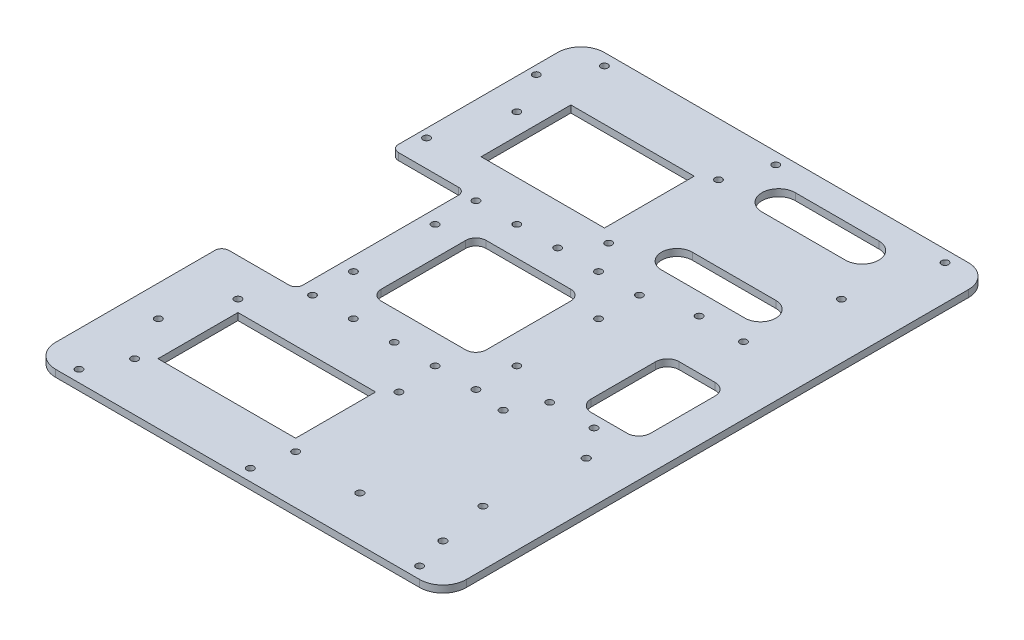
SolidWorks part; units mm, degrees
ref_plane "前视基准面" through (0, 0, 0) normal (0, 0, 1) x (1, 0, 0)
ref_plane "上视基准面" through (0, 0, 0) normal (0, 1, 0) x (1, 0, 0)
ref_plane "右视基准面" through (0, 0, 0) normal (1, 0, 0) x (0, 0, -1)
other "Configuration Table"
sketch "草图2" plane through (0, 0, 0) normal (0, 1, 0) x (1, 0, 0)
  line L0 (0, 0) -> (34826.5103, 0) construction
  line L1 (0, 0) -> (0, -34826.5103) construction
  line L2 (-72.5, -36.2939) -> (-72.5, -107.5)
  line L4 (-72.5, 107.5) -> (-72.5, 36.2939)
  line L7 (-62.5, 117.5) -> (93.3866, 117.5)
  line L8 (-62.5, -117.5) -> (93.3866, -117.5)
  line L15 (-35, 35) -> (35, 35) construction
  line L16 (-35, 35) -> (-35, -35) construction
  line L17 (-35, -35) -> (35, -35) construction
  line L18 (35, 35) -> (35, -35) construction
  line L19 (-35, 35) -> (35, -35) construction
  line L20 (-35, -35) -> (35, 35) construction
  line L21 (-18.1, 22.5) -> (18.1, 22.5)
  line L22 (-22.5, 18.1) -> (-22.5, -18.1)
  line L23 (-18.1, -22.5) -> (18.1, -22.5)
  line L24 (22.5, 18.1) -> (22.5, -18.1)
  line L25 (-22.5, 22.5) -> (22.5, -22.5) construction
  line L26 (-22.5, -22.5) -> (22.5, 22.5) construction
  line L30 (103.3866, 107.5) -> (103.3866, -107.5)
  line L32 (-49.5097, -52.4041) -> (-49.5097, -96.6641) construction
  line L33 (-72.5, -36.2939) -> (-40.7785, -36.2939)
  line L35 (-72.5, 36.2939) -> (-40.7785, 36.2939)
  line L36 (-40.7785, -36.2939) -> (-40.7785, 36.2939)
  line L37 (-49.5097, -96.6641) -> (19.4403, -96.6641) construction
  line L38 (19.4403, -52.4041) -> (19.4403, -96.6641) construction
  line L39 (-49.5097, -52.4041) -> (19.4403, -52.4041) construction
  line L40 (-44.5097, -57.4041) -> (-44.5097, -91.6641)
  line L41 (88.614, 18.8414) -> (63.156, 18.8414)
  line L42 (88.614, 18.8414) -> (88.614, -18.8414)
  line L43 (88.614, -18.8414) -> (63.156, -18.8414)
  line L44 (63.156, 18.8414) -> (63.156, -18.8414)
  line L45 (-44.5097, -91.6641) -> (14.4403, -91.6641)
  line L46 (14.4403, -57.4041) -> (14.4403, -91.6641)
  line L47 (-44.5097, -57.4041) -> (14.4403, -57.4041)
  line L49 (-50.2176, 90.862) -> (2.6188, 90.862)
  line L50 (-50.2176, 90.862) -> (-50.2176, 52.4282)
  line L51 (-50.2176, 52.4282) -> (2.6188, 52.4282)
  line L52 (2.6188, 90.862) -> (2.6188, 52.4282)
  circle A4 centre (-35, 35) radius 1.5
  circle A5 centre (35, 35) radius 1.5
  circle A6 centre (35, -35) radius 1.5
  circle A7 centre (-35, -35) radius 1.5
  arc A8 (-22.5, -18.1) -> (-18.1, -22.5) centre (-18.1, -18.1) ccw
  arc A9 (18.1, -22.5) -> (22.5, -18.1) centre (18.1, -18.1) ccw
  arc A10 (18.1, 22.5) -> (22.5, 18.1) centre (18.1, 18.1) cw
  arc A11 (-18.1, 22.5) -> (-22.5, 18.1) centre (-18.1, 18.1) ccw
  circle A12 centre (-17.5, 35) radius 1.5
  circle A13 centre (17.5, 35) radius 1.5
  circle A14 centre (-17.5, -35) radius 1.5
  circle A15 centre (17.5, -35) radius 1.5
  circle A16 centre (-35, 17.5) radius 1.5
  circle A17 centre (-35, -17.5) radius 1.5
  circle A18 centre (35, -17.5) radius 1.5
  circle A19 centre (35, 17.5) radius 1.5
  circle A20 centre (0, 35) radius 1.5
  circle A21 centre (0, -35) radius 1.5
  arc A22 (-62.5, 117.5) -> (-72.5, 107.5) centre (-62.5, 107.5) ccw
  arc A23 (-72.5, -107.5) -> (-62.5, -117.5) centre (-62.5, -107.5) ccw
  arc A24 (103.3866, -107.5) -> (93.3866, -117.5) centre (93.3866, -107.5) cw
  arc A25 (93.3866, 117.5) -> (103.3866, 107.5) centre (93.3866, 107.5) cw
  circle A34 centre (-49.5097, -52.4041) radius 1.5
  circle A35 centre (-49.5097, -96.6641) radius 1.5
  circle A36 centre (19.4403, -52.4041) radius 1.5
  circle A37 centre (19.4403, -96.6641) radius 1.5
  circle A38 centre (-59.25, -76.75) radius 1.5
  circle A39 centre (79.75, -76.75) radius 1.5
  circle A40 centre (79.75, 76.75) radius 1.5
  circle A41 centre (-59.25, 76.75) radius 1.5
  circle A42 centre (-68.8711, 94.7111) radius 1.5
  circle A43 centre (-68.8711, 47.7111) radius 1.5
  circle A44 centre (9.1289, 47.7111) radius 1.5
  circle A45 centre (9.1289, 94.7111) radius 1.5
  circle A46 centre (48.5314, -36.8541) radius 1.55
  circle A47 centre (84.0914, -36.8541) radius 1.55
  circle A48 centre (48.5314, -98.2341) radius 1.55
  circle A49 centre (84.0914, -98.2341) radius 1.55
  circle A54 centre (74.5534, 40.0159) radius 1.5
  circle A55 centre (55.5534, 40.0159) radius 1.5
  circle A56 centre (74.5534, -23.9841) radius 1.5
  circle A57 centre (55.5534, -23.9841) radius 1.5
  point P5 (0, 0)
  point P10 (0, 0)
  point P11 (0, 0)
  point P19 (0, 0)
  point P40 (-72.5, 117.5)
  point P43 (-72.5, -117.5)
  dimension "D3" = 45
  dimension "D4" = 3
  dimension "D6" = 4.4
  dimension "D7" = 17.5
  dimension "D8" = 3
  dimension "D9" = 3
  dimension "D11" = 3
  dimension "D12" = 3
  dimension "D14" = 10
  dimension "D16" = 68.95
  dimension "D2" = 45
  dimension "D5" = 70
  dimension "D10" = 17.5
  dimension "D13" = 235
  dimension "D15" = 44.26
  dimension "D17" = 5
extrude "凸台-拉伸2" add sketch "草图2" along normal blind 3
fillet "圆角2" radius 3 4 edges at (-40.7785, 1.5, 36.2939) (-40.7785, 1.5, -36.2939) (-72.5, 1.5, 36.2939) (-72.5, 1.5, -36.2939)
fillet "圆角3" radius 5 4 edges at (88.614, 1.5, -18.8414) (63.156, 1.5, -18.8414) (63.156, 1.5, 18.8414) (88.614, 1.5, 18.8414)
sketch "草图3" plane through (0, 3, 0) normal (0, 1, 0) x (1, 0, 0)
  line L0 (30.3803, 99.2435) -> (66.1384, 99.2435) construction
  line L1 (30.3803, 106.3927) -> (66.1384, 106.3927)
  line L2 (30.3803, 92.0943) -> (66.1384, 92.0943)
  line L3 (30.3803, 55.6763) -> (66.1384, 55.6763) construction
  line L4 (30.3803, 62.2745) -> (66.1384, 62.2745)
  line L5 (30.3803, 49.0781) -> (66.1384, 49.0781)
  arc A0 (30.3803, 106.3927) -> (30.3803, 92.0943) centre (30.3803, 99.2435) ccw
  arc A1 (66.1384, 92.0943) -> (66.1384, 106.3927) centre (66.1384, 99.2435) ccw
  arc A2 (30.3803, 62.2745) -> (30.3803, 49.0781) centre (30.3803, 55.6763) ccw
  arc A3 (66.1384, 49.0781) -> (66.1384, 62.2745) centre (66.1384, 55.6763) ccw
  point P2 (48.2593, 99.2435)
  point P7 (48.2593, 55.6763)
extrude "切除-拉伸1" cut sketch "草图3" against normal through all
sketch "草图4" plane through (0, 3, 0) normal (0, 1, 0) x (1, 0, 0)
  line L0 (-63.4095, -112.5) -> (93.6727, -112.5) construction
  line L1 (-63.4095, 112.5) -> (94.67, 112.5) construction
  line L3 (93.3866, 117.5) -> (-62.5, 117.5) construction
  line L4 (-62.5, -117.5) -> (93.3866, -117.5) construction
  line L5 (103.3866, -107.5) -> (103.3866, 107.5) construction
  line L6 (-72.5, -39.2939) -> (-72.5, -107.5) construction
  line L7 (-72.5, 107.5) -> (-72.5, 39.2939) construction
  circle A1 centre (-57.5, -112.5) radius 1.5
  circle A2 centre (15.8866, -112.5) radius 1.5
  circle A3 centre (88.3866, -112.5) radius 1.5
  circle A4 centre (88.3866, 112.5) radius 1.5
  circle A5 centre (15.8866, 112.5) radius 1.5
  circle A6 centre (-57.5, 112.5) radius 1.5
  dimension "D1" = 3
  dimension "D2" = 3
  dimension "D3" = 3
  dimension "D4" = 3
  dimension "D5" = 3
  dimension "D6" = 3
  dimension "D7" = 5
  dimension "D8" = 5
  dimension "D9" = 15
  dimension "D10" = 15
  dimension "D11" = 15
  dimension "D12" = 15
  dimension "D13" = 72.5
  dimension "D14" = 72.5
extrude "切除-拉伸2" cut sketch "草图4" against normal blind 10
